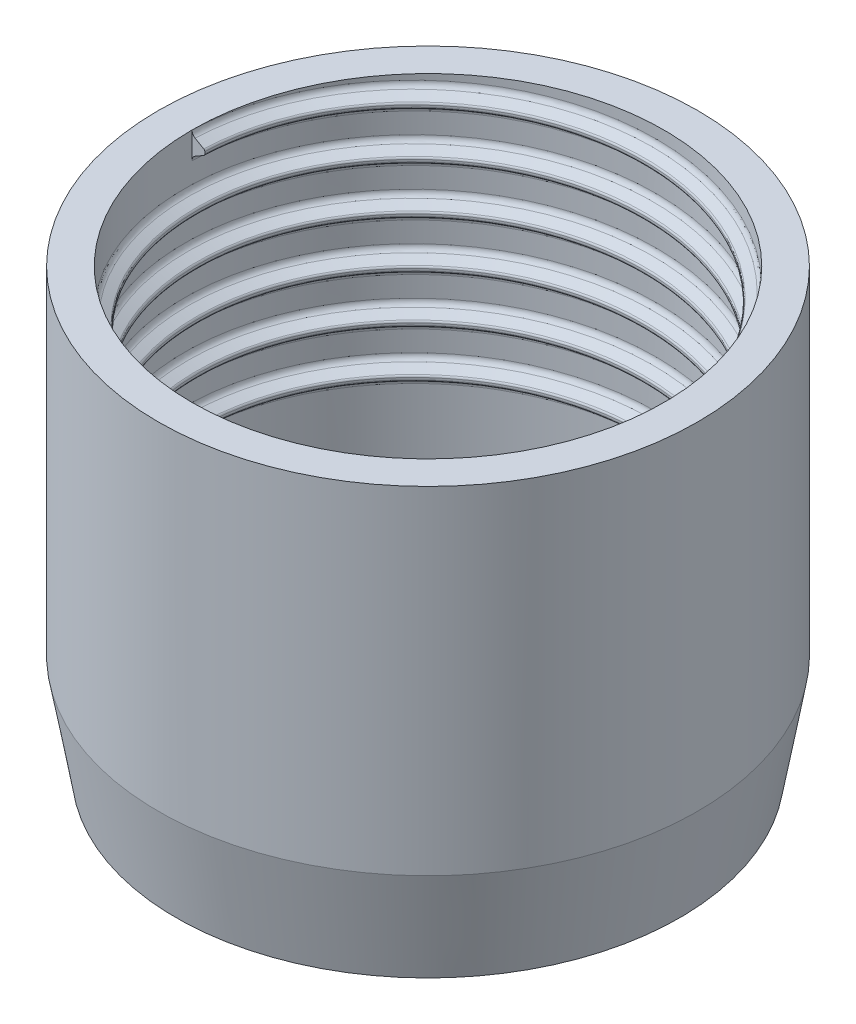
SolidWorks part; units mm, degrees
ref_plane "Front Plane" through (0, 0, 0) normal (0, 0, 1) x (1, 0, 0)
ref_plane "Top Plane" through (0, 0, 0) normal (0, 1, 0) x (1, 0, 0)
ref_plane "Right Plane" through (0, 0, 0) normal (1, 0, 0) x (0, 0, -1)
sketch "Sketch1" plane through (0, 0, 0) normal (0, 1, 0) x (1, 0, 0)
  circle A0 centre (0, 0) radius 16
extrude "Boss-Extrude1" add sketch "Sketch1" along normal blind 20 contours A0
sketch "Sketch2" plane through (0, 20, 0) normal (0, 1, 0) x (1, 0, 0)
  circle A0 centre (0, 0) radius 14
sketch "Sketch10" plane through (0, 20, 0) normal (0, 1, 0) x (1, 0, 0)
  circle A0 centre (0, 0) radius 14
extrude "Cut-Extrude2" cut sketch "Sketch10" against normal blind 20
thread "Thread1" pitch 2.1167 method extrude profile "Thread Profile2" start angle 0, offset 0, length 16, pitch 2.8, diameter 28
ref_plane "Plane2" through (-14, 20, 0) normal (0, 0, -1) x (1, 0, 0)
sketch "Thread Profile2" plane through (-14, 20, 0) normal (0, 0, -1) x (1, 0, 0)
  line L0 (0, 0) -> (0, 2.1167) construction
  line L1 (0, 0) -> (0, 1.5829)
  line L2 (0.381, 1.5829) -> (0.762, 1.5829) construction
  line L3 (0.762, 0.8497) -> (0.762, 0.7332)
  line L4 (0.6985, 0.9597) -> (0.1905, 1.253)
  line L5 (0.6985, 0.6232) -> (0.1905, 0.33)
  line L6 (0.381, 0) -> (0.762, 0) construction
  arc A0 (0.1905, 1.253) -> (0, 1.5829) centre (0.381, 1.5829) cw
  arc A1 (0.1905, 0.33) -> (0, 0) centre (0.381, 0) ccw
  arc A2 (0.762, 0.7332) -> (0.6985, 0.6232) centre (0.635, 0.7332) cw
  arc A3 (0.762, 0.8497) -> (0.6985, 0.9597) centre (0.635, 0.8497) ccw
  point P10 (0.762, 0.923)
  point P17 (0.762, 0.6599)
  point P18 (0, 1.363)
  point P19 (0, 0.22)
  point P20 (0, 0)
  dimension "RootFillet1" = 0.381
  dimension "RootFillet2" = 0.381
  dimension "CrestFillet2" = 0.127
  dimension "CrestFillet1" = 0.127
  dimension "Pitch" = 2.1167
  dimension "Angle1" = 30
  dimension "Angle2" = 30
  dimension "a" = 1.143
  dimension "b" = 0.762
  dimension "c" = 0.2631
sketch "Sketch19" plane through (0, 0, 0) normal (0, -1, 0) x (-1, 0, 0)
  circle A0 centre (0, 0) radius 13
  circle A1 centre (0, 0) radius 6.6
sketch "Sketch20" plane through (0, 0, 0) normal (0, -1, 0) x (1, 0, 0)
  circle A0 centre (0, 0) radius 16
extrude "Boss-Extrude3" add sketch "Sketch20" along normal blind 6 draft 10
extrude "Cut-Extrude3" cut sketch "Sketch19" along normal blind 3 contours A1
sketch "Sketch127" plane through (0, -3, 0) normal (0, 1, 0) x (1, 0, 0)
  circle A0 centre (0, 0) radius 5
extrude "Cut-Extrude4" cut sketch "Sketch127" against normal blind 3
